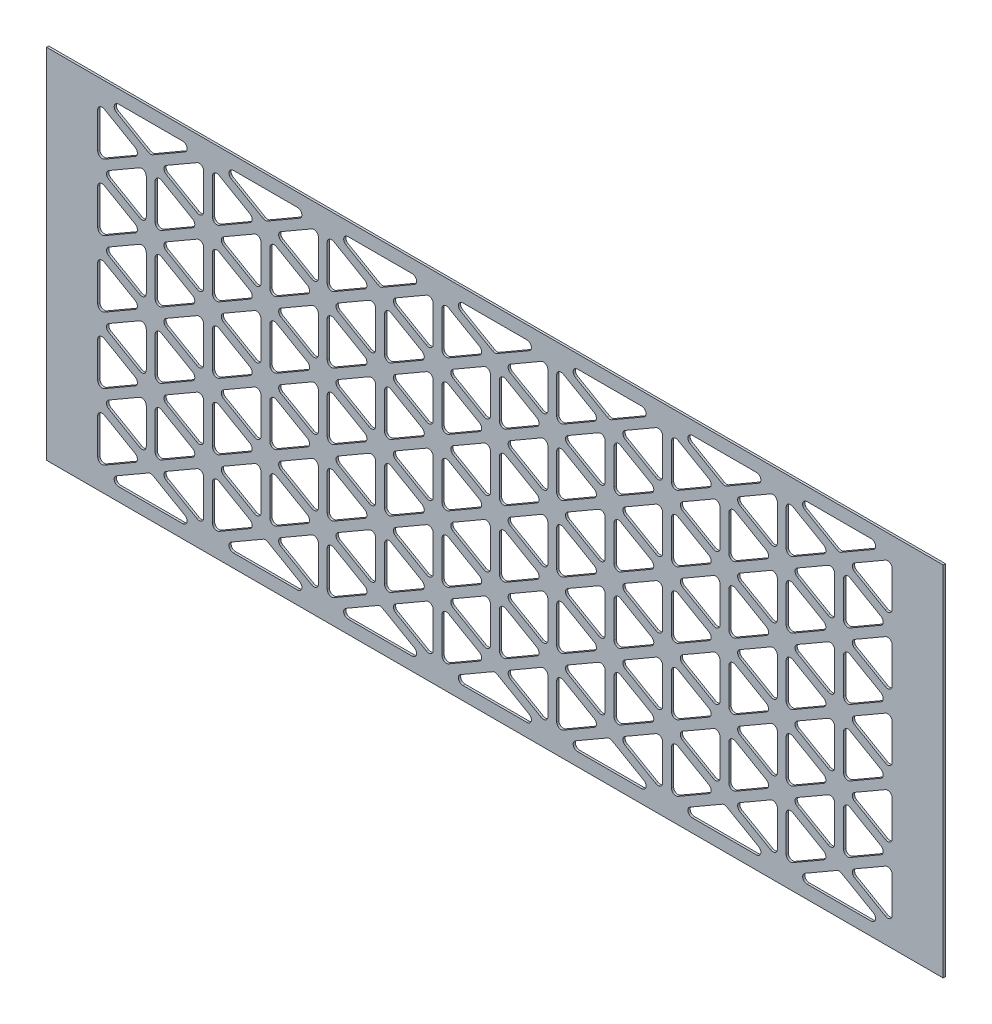
SolidWorks part; units mm, degrees
ref_plane "Front Plane" through (0, 0, 0) normal (0, 0, 1) x (1, 0, 0)
ref_plane "Top Plane" through (0, 0, 0) normal (0, 1, 0) x (1, 0, 0)
ref_plane "Right Plane" through (0, 0, 0) normal (1, 0, 0) x (0, 0, -1)
sketch "Sketch1" plane through (0, 0, 0) normal (0, 0, 1) x (1, 0, 0)
  line L1 (-101.5, 40.5) -> (101.5, 40.5)
  line L2 (-101.5, 40.5) -> (-101.5, -40.5)
  line L3 (-101.5, -40.5) -> (101.5, -40.5)
  line L4 (101.5, 40.5) -> (101.5, -40.5)
  line L5 (-101.5, 40.5) -> (101.5, -40.5) construction
  line L6 (-101.5, -40.5) -> (101.5, 40.5) construction
  point P0 (0, 0)
  dimension "D1" = 81
  dimension "D2" = 203
extrude "Boss-Extrude1" add sketch "Sketch1" along normal mid plane 0.5
sketch "Sketch3" plane through (0, 0, 0.25) normal (0, 0, 1) x (1, 0, 0)
  line L0 (-90.93, -22.5) -> (-90.93, -37.5) construction
  line L1 (-90.93, -37.5) -> (-77.9396, -30) construction
  line L2 (-77.9396, -30) -> (-90.93, -22.5) construction
  line L3 (-77.9396, -30) -> (-77.9396, -15) construction
  line L4 (-77.9396, -15) -> (-90.93, -22.5) construction
  line L7 (-89.93, -24.2321) -> (-89.93, -35.7679) construction
  line L8 (-89.93, -35.7679) -> (-79.9396, -30) construction
  line L9 (-79.9396, -30) -> (-89.93, -24.2321) construction
  line L10 (-78.9396, -16.7321) -> (-78.9396, -28.2679) construction
  line L11 (-78.9396, -28.2679) -> (-88.93, -22.5) construction
  line L12 (-88.93, -22.5) -> (-78.9396, -16.7321) construction
  line L13 (-101.5, -40.5) -> (101.5, -40.5) construction
  line L15 (-101.5, 40.5) -> (-101.5, -40.5) construction
  line L16 (-90.93, -30) -> (-89.93, -30) construction
  line L17 (-84.4348, -26.25) -> (-84.9348, -27.116) construction
  line L18 (-84.4348, -33.75) -> (-84.9348, -32.884) construction
  line L19 (-89.93, -25.9641) -> (-89.93, -34.0359)
  line L20 (-88.43, -34.9019) -> (-81.4396, -30.866)
  line L21 (-81.4396, -29.134) -> (-88.43, -25.0981)
  line L23 (-78.9396, -18.4641) -> (-78.9396, -26.5359)
  line L24 (-87.43, -23.366) -> (-80.4396, -27.4019)
  line L25 (-87.43, -21.634) -> (-80.4396, -17.5981)
  arc A0 (-88.43, -34.9019) -> (-89.93, -34.0359) centre (-88.93, -34.0359) cw
  arc A1 (-81.4396, -29.134) -> (-81.4396, -30.866) centre (-81.9396, -30) cw
  arc A2 (-89.93, -25.9641) -> (-88.43, -25.0981) centre (-88.93, -25.9641) cw
  arc A4 (-87.43, -23.366) -> (-87.43, -21.634) centre (-86.93, -22.5) cw
  arc A5 (-78.9396, -26.5359) -> (-80.4396, -27.4019) centre (-79.9396, -26.5359) cw
  arc A6 (-78.9396, -18.4641) -> (-80.4396, -17.5981) centre (-79.9396, -18.4641) ccw
  dimension "D7" = 1
  dimension "D9" = 1
  dimension "D1" = 2
  dimension "D2" = 15
  dimension "D3" = 3
  dimension "D4" = 10.57
  dimension "D5" = 1
  dimension "D6" = 1
  dimension "length" = 12.9904
extrude "Cut-Extrude3" cut sketch "Sketch3" against normal through all contours L21 A2 L19 A0 L20 A1
extrude "Cut-Extrude4" cut sketch "Sketch3<5>" against normal through all contours A6 L23 A5 L24 A4 L25
sketch "Sketch3<5>" plane through (0, 0, 0.25) normal (0, 0, 1) x (1, 0, 0) same geometry as "Sketch3"
pattern_linear "LPattern2" count 5 spacing 15 along (0, 1, 0) of "Cut-Extrude3"
pattern_linear "LPattern3" count 4 spacing 15 along (0, 1, 0) of "Cut-Extrude4"
ref_plane "Plane1" through (-77.9396, 0, 0) normal (-1, 0, 0) x (0, 0, 1)
mirror "Mirror1" about plane through (-77.9396, 0, 0) normal (-1, 0, 0) of "LPattern2", "LPattern3"
pattern_linear "LPattern4" count 7 spacing 25.98 along (1, 0, 0) of "LPattern3", "LPattern2", "Mirror1"
sketch "Sketch7" plane through (0, 0, 0.25) normal (0, 0, 1) x (1, 0, 0)
  line L0 (-90.93, -37.5) -> (-77.94, -30) construction
  line L1 (-77.94, -30) -> (-64.95, -37.5) construction
  line L2 (-64.95, -37.5) -> (-90.93, -37.5) construction
  line L3 (-101.5, -40.5) -> (101.5, -40.5) construction
  line L4 (-101.5, 40.5) -> (-101.5, -40.5) construction
  line L5 (-78.44, -31.4434) -> (-85.6981, -35.634)
  line L6 (-85.1981, -37.5) -> (-70.6819, -37.5)
  line L7 (-70.1819, -35.634) -> (-77.44, -31.4434)
  arc A0 (-85.1981, -37.5) -> (-85.6981, -35.634) centre (-85.1981, -36.5) cw
  arc A1 (-70.1819, -35.634) -> (-70.6819, -37.5) centre (-70.6819, -36.5) cw
  arc A2 (-77.44, -31.4434) -> (-78.44, -31.4434) centre (-77.94, -32.3094) ccw
  point P9 (-71.445, -33.75)
  dimension "D7" = 1
  dimension "D1" = 10.57
  dimension "D2" = 3
  dimension "D3" = 25.98
  dimension "D4" = 7.5
  dimension "D5" = 1
  dimension "D6" = 1
extrude "Cut-Extrude5" cut sketch "Sketch7" against normal through all
pattern_linear "LPattern5" count 7 spacing 25.98 along (1, 0, 0) of "Cut-Extrude5"
ref_plane "Plane2" [suppressed] through (0, 0, 0) normal (0, -1, 0) x (-1, 0, 0)
mirror "Mirror2" about plane through (0, 0, 0) normal (0, -1, 0) of "LPattern5"
equation "\"D3@LPattern4\"=2*12.99"
